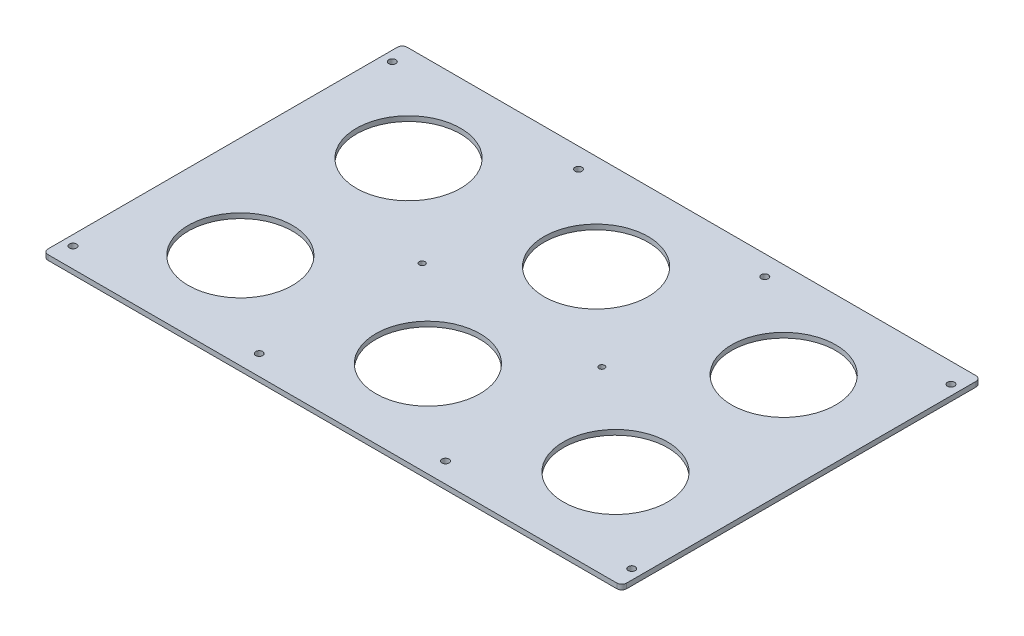
SolidWorks part; units mm, degrees
material "ABS"
ref_plane "Front" through (0, 0, 0) normal (0, 0, 1) x (1, 0, 0)
ref_plane "Top" through (0, 0, 0) normal (0, 1, 0) x (1, 0, 0)
ref_plane "Right" through (0, 0, 0) normal (1, 0, 0) x (0, 0, -1)
sketch "Sketch1" plane through (0, 0, 0) normal (0, 1, 0) x (1, 0, 0)
  line L1 (-180.975, 114.3) -> (180.975, 114.3)
  line L2 (-184.15, 111.125) -> (-184.15, -111.125)
  line L3 (-180.975, -114.3) -> (180.975, -114.3)
  line L4 (184.15, 111.125) -> (184.15, -111.125)
  line L5 (-184.15, 114.3) -> (184.15, -114.3) construction
  line L6 (-184.15, -114.3) -> (184.15, 114.3) construction
  circle A0 centre (119.38, -53.5178) radius 33.147
  arc A1 (-184.15, -111.125) -> (-180.975, -114.3) centre (-180.975, -111.125) ccw
  arc A2 (180.975, -114.3) -> (184.15, -111.125) centre (180.975, -111.125) ccw
  arc A3 (184.15, 111.125) -> (180.975, 114.3) centre (180.975, 111.125) ccw
  arc A4 (-180.975, 114.3) -> (-184.15, 111.125) centre (-180.975, 111.125) ccw
  circle A5 centre (-177.8, -101.6) radius 2.2479 construction
  circle A6 centre (-59.2667, -101.6) radius 2.2479 construction
  circle A7 centre (59.2667, -101.6) radius 2.2479 construction
  circle A8 centre (177.8, -101.6) radius 2.2479 construction
  circle A9 centre (177.8, 101.6) radius 2.2479 construction
  circle A10 centre (59.2667, 101.6) radius 2.2479 construction
  circle A11 centre (-59.2667, 101.6) radius 2.2479 construction
  circle A12 centre (-177.8, 101.6) radius 2.2479 construction
  circle A13 centre (-177.8, -101.6) radius 2.2479
  circle A14 centre (-59.2667, -101.6) radius 2.2479
  circle A15 centre (59.2667, -101.6) radius 2.2479
  circle A16 centre (177.8, -101.6) radius 2.2479
  circle A17 centre (177.8, 101.6) radius 2.2479
  circle A18 centre (59.2667, 101.6) radius 2.2479
  circle A19 centre (-59.2667, 101.6) radius 2.2479
  circle A20 centre (-177.8, 101.6) radius 2.2479
  circle A21 centre (-57.15, 0) radius 1.8288 construction
  circle A22 centre (57.15, 0) radius 1.8288 construction
  circle A23 centre (-57.15, 0) radius 1.8288
  circle A24 centre (57.15, 0) radius 1.8288
  circle A25 centre (119.38, 53.5178) radius 33.147
  circle A26 centre (0, 53.5178) radius 33.147
  circle A27 centre (0, -53.5178) radius 33.147
  circle A28 centre (-119.38, 53.5178) radius 33.147
  circle A29 centre (-119.38, -53.5178) radius 33.147
  point P0 (0, 0)
  dimension "D3" = 66.294
  dimension "D4" = 3.175
  dimension "D1" = 368.3
  dimension "D2" = 228.6
extrude "Boss-Extrude1" add sketch "Sketch1" along normal blind 3.175
